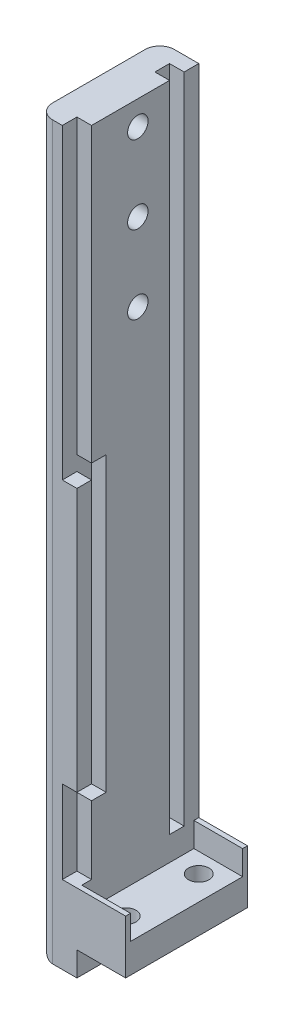
SolidWorks part; units mm, degrees
material "ABS"
ref_plane "前基準面" through (0, 0, 0) normal (0, 0, 1) x (1, 0, 0)
ref_plane "上基準面" through (0, 0, 0) normal (0, 1, 0) x (1, 0, 0)
ref_plane "右基準面" through (0, 0, 0) normal (1, 0, 0) x (0, 0, -1)
sketch "草圖1" plane through (0, 0, 0) normal (0, 0, 1) x (1, 0, 0)
  line L0 (-18, 116.9353) -> (-10, 116.9353)
  line L1 (-10, 116.9353) -> (-10, -22.0647)
  line L2 (-10, -22.0647) -> (0, -22.0647)
  line L3 (0, -22.0647) -> (0, -28.0647)
  line L4 (0, -28.0647) -> (-10, -28.0647)
  line L5 (-10, -28.0647) -> (-10, -33.0647)
  line L6 (-10, -33.0647) -> (-18, -33.0647)
  line L7 (-18, -33.0647) -> (-18, 116.9353)
  dimension "D1" = 10
  dimension "D2" = 10
  dimension "D3" = 6
  dimension "D4" = 8
  dimension "D5" = 150
  dimension "D6" = 5
extrude "填料-伸長1" add sketch "草圖1" along normal blind 25
sketch "草圖2" plane through (0, -22.0647, 0) normal (0, 1, 0) x (1, 0, 0)
  line L0 (0, -25) -> (0, 0) construction
  line L1 (0, 0) -> (-10, 0) construction
  circle A0 centre (-5, -5) radius 2.1
  circle A1 centre (-5, -20) radius 2.1
  dimension "D1" = 5
  dimension "D2" = 5
  dimension "D3" = 4.2
  dimension "D4" = 2
extrude "除料-伸長1" cut sketch "草圖2" against normal blind 25
sketch "草圖3" plane through (-18, 0, 0) normal (-1, 0, 0) x (0, 0, 1)
  line L0 (25, 116.9353) -> (0, 116.9353) construction
  line L1 (25, 116.9353) -> (25, -33.0647) construction
  circle A0 centre (12.5, 111.9353) radius 2.1
  circle A1 centre (12.5, 95.9353) radius 2.1
  circle A2 centre (12.5, 79.9353) radius 2.1
  point P4 (12.5, 116.9353)
  dimension "D1" = 4.2
  dimension "D2" = 5
  dimension "D3" = 12.5
  dimension "D5" = 16
  dimension "D4" = 3
extrude "除料-伸長2" cut sketch "草圖3" against normal blind 25
sketch "草圖4" plane through (0, -22.0647, 0) normal (0, 1, 0) x (1, 0, 0)
  line L0 (-10, -25) -> (-10, 0) construction
  line L1 (0, 0) -> (-10, 0)
  line L2 (0, 0) -> (0, -1)
  line L3 (0, -1) -> (-10, -1)
  line L4 (-10, 0) -> (-10, -1)
  line L6 (0, -25) -> (-10, -25)
  line L7 (0, -25) -> (0, -24)
  line L8 (0, -24) -> (-10, -24)
  line L9 (-10, -25) -> (-10, -24)
  dimension "D1" = 1
  dimension "D2" = 1
extrude "填料-伸長2" add sketch "草圖4" along normal blind 5
sketch "草圖5" plane through (0, 116.9353, 0) normal (0, 1, 0) x (1, 0, 0)
  line L0 (-10, -25) -> (-10, 0) construction
  line L6 (-10, -6) -> (-13, -6)
  line L7 (-10, -6) -> (-10, -3)
  line L8 (-10, -3) -> (-13, -3)
  line L9 (-13, -6) -> (-13, -3)
  line L10 (-10, 0) -> (-18, 0) construction
  dimension "D2" = 3
  dimension "D3" = 3
  dimension "D6" = 3
extrude "除料-伸長3" cut sketch "草圖5" against normal up to surface (134 mm away) up to face at (-5, -17.0647, 24.5)
fillet "圓角1" radius 3 3 edges at (-18, -33.0647, 12.5) (-18, 41.9353, 25) (-18, 41.9353, 0)
sketch "草圖6" plane through (0, 116.9353, 0) normal (0, 1, 0) x (1, 0, 0)
  line L1 (-10, -25) -> (-13, -25)
  line L2 (-10, -25) -> (-10, -22)
  line L3 (-10, -22) -> (-13, -22)
  line L4 (-13, -25) -> (-13, -22)
  dimension "D1" = 3
  dimension "D2" = 3
extrude "除料-伸長4" cut sketch "草圖6" against normal blind 60
sketch "草圖7" plane through (-10, 0, 0) normal (1, 0, 0) x (0, 0, -1)
  line L1 (-22, 56.9353) -> (-19, 56.9353)
  line L2 (-22, 56.9353) -> (-22, -3.0647)
  line L3 (-22, -3.0647) -> (-19, -3.0647)
  line L4 (-19, 56.9353) -> (-19, -3.0647)
  line L5 (-22, -3.0647) -> (-25, -3.0647)
  line L6 (-22, -3.0647) -> (-22, -17.0647)
  line L7 (-22, -17.0647) -> (-25, -17.0647)
  line L8 (-25, -3.0647) -> (-25, -17.0647)
  line L9 (-25, -3.0647) -> (-22, -3.0647)
  line L10 (-25, -3.0647) -> (-25, -0.0647)
  line L11 (-25, -0.0647) -> (-22, -0.0647)
  line L12 (-22, -3.0647) -> (-22, -0.0647)
  line L13 (-25, 56.9353) -> (-22, 56.9353)
  line L14 (-25, 56.9353) -> (-25, 53.9353)
  line L15 (-25, 53.9353) -> (-22, 53.9353)
  line L16 (-22, 56.9353) -> (-22, 53.9353)
  line M7 (-22, 56.9353) -> (-25, 56.9353)
  line M8 (-25, 56.9353) -> (-25, -17.0647)
  line M9 (-25, -17.0647) -> (-24, -17.0647)
  dimension "D1" = 3
  dimension "D2" = 60
  dimension "D3" = 3
  dimension "D4" = 3
extrude "除料-伸長7" cut sketch "草圖7" against normal blind 3 contours L7 L6 L5 M8 M9 | L11 L5 L2 M8 | L4 L1 L2 L3 | L15 L2 M8 M7 region at (-10, 26.9353, 20.5) region at (-10, 55.4353, 23.5) region at (-10, -1.5647, 23.5) region at (-10, -10.0647, 23.5)
sketch "草圖8" plane through (-18, 0, 0) normal (-1, 0, 0) x (0, 0, 1)
  text T0 "            left down side" font "Comic Sans MS" height in points 26
extrude "除料-伸長8" cut sketch "草圖8" against normal blind 2
